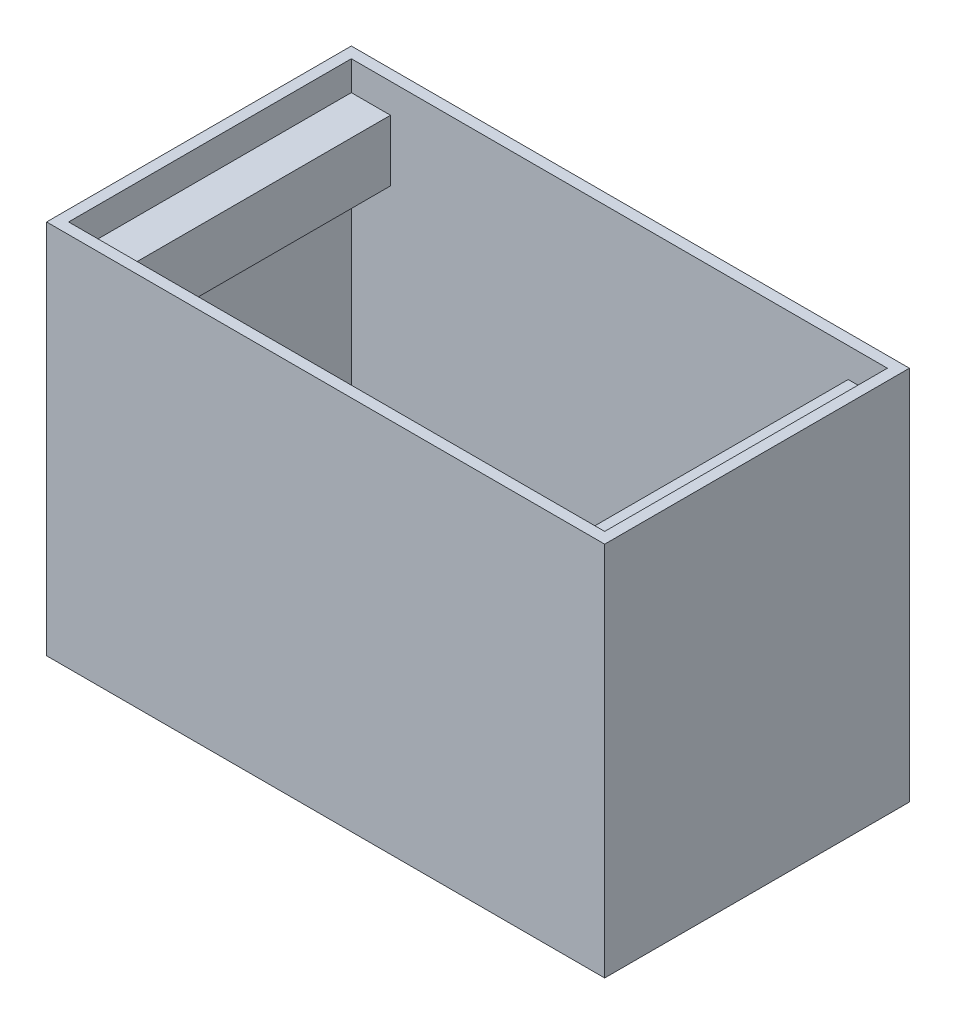
SolidWorks part; units mm, degrees
ref_plane "Front Plane" through (0, 0, 0) normal (0, 0, 1) x (1, 0, 0)
ref_plane "Top Plane" through (0, 0, 0) normal (0, 1, 0) x (1, 0, 0)
ref_plane "Right Plane" through (0, 0, 0) normal (1, 0, 0) x (0, 0, -1)
sketch "Sketch1" plane through (0, 0, 0) normal (0, 1, 0) x (1, 0, 0)
  line L0 (-228, -124.5) -> (-228, 124.5)
  line L1 (-219, -115.5) -> (219, -115.5)
  line L2 (-219, -115.5) -> (-219, 115.5)
  line L3 (-219, 115.5) -> (219, 115.5)
  line L4 (219, -115.5) -> (219, 115.5)
  line L5 (-219, -115.5) -> (219, 115.5) construction
  line L6 (-219, 115.5) -> (219, -115.5) construction
  line L7 (-228, 124.5) -> (228, 124.5)
  line L8 (228, -124.5) -> (228, 124.5)
  line L9 (-228, -124.5) -> (228, -124.5)
  point P0 (0, 0)
  dimension "D2" = 231
  dimension "D3" = 438
  dimension "D1" = 9
sketch "Sketch2" plane through (0, 0, 0) normal (0, 0, 1) x (1, 0, 0)
  line L0 (0, 0) -> (0, 80) construction
  line L1 (0, 80) -> (0, 298) construction
  line L2 (0, 298) -> (0, 299) construction
  line L3 (0, 0) -> (0, -9) construction
  line L4 (-219, 0) -> (-228, 0) construction
  dimension "D1" = 1
  dimension "D2" = 218
  dimension "D3" = 80
extrude "Boss-Extrude1" add sketch "Sketch1" against normal up to vertex (9 mm away) contours L1 L4 L3 L2 | L0 L9 L8 L7 L4 L1 L2 L3 region at (-222.8045, 0, 0) region at (0, 0, 0) up to point (0, -9, 0)
extrude "Boss-Extrude2" add sketch "Sketch1<3>" along normal up to vertex (298 mm away) up to point (0, 298, 0)
sketch "Sketch1<3>" plane through (0, 0, 0) normal (0, 1, 0) x (1, 0, 0) same geometry as "Sketch1"
sketch "Sketch3" plane through (-219, 0, 0) normal (1, 0, 0) x (0, 0, -1)
  line L0 (0, 249) -> (0, 0) construction
  line L1 (-115.5, 224) -> (115.5, 224)
  line L2 (-115.5, 224) -> (-115.5, 274)
  line L3 (-115.5, 274) -> (115.5, 274)
  line L4 (115.5, 224) -> (115.5, 274)
  line L5 (-115.5, 224) -> (115.5, 274) construction
  line L6 (-115.5, 274) -> (115.5, 224) construction
  line L7 (115.5, 0) -> (-115.5, 0) construction
  line L8 (115.5, 298) -> (115.5, 0) construction
  line L9 (115.5, 298) -> (-115.5, 298) construction
  point P0 (0, 249)
  dimension "D1" = 50
  dimension "D2" = 24
extrude "Boss-Extrude3" add sketch "Sketch3" along normal blind 32
mirror "Mirror1" about plane through (0, 0, 0) normal (1, 0, 0) of "Boss-Extrude3"
